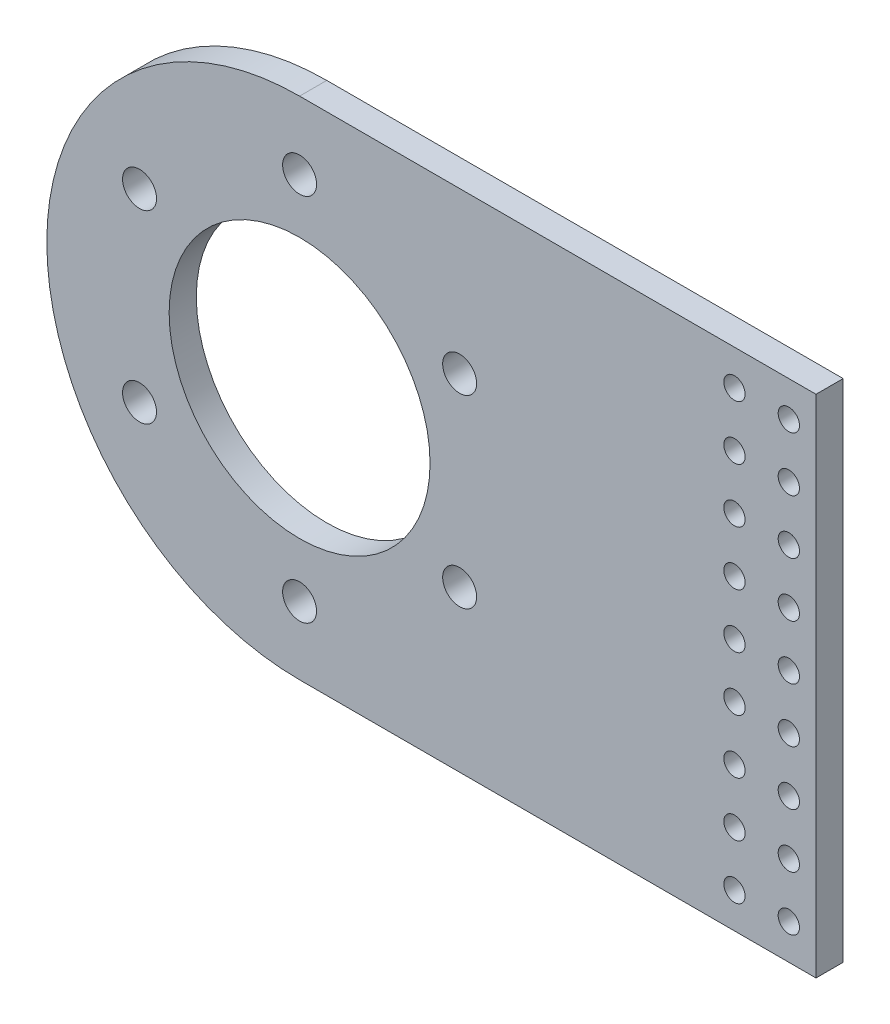
SolidWorks part; units mm, degrees
ref_plane "Front Plane" through (0, 0, 0) normal (1, 0, 0) x (0, 1, 0)
ref_plane "Top Plane" through (0, 0, 0) normal (0, 0, 1) x (0, 1, 0)
ref_plane "Right Plane" through (0, 0, 0) normal (0, 1, 0) x (-1, 0, 0)
sketch "Sketch1" plane through (0, 0, 0) normal (0, 0, 1) x (0, 1, 0)
  line L0 (-59.055, 0) -> (-59.055, -120.65)
  line L1 (-59.055, -120.65) -> (59.055, -120.65)
  line L2 (59.055, -120.65) -> (59.055, 0)
  circle A0 centre (0, 0) radius 25.4 construction
  circle A1 centre (0, 0) radius 27.305 construction
  circle A2 centre (0, 0) radius 43.18 construction
  circle A3 centre (-43.18, 0) radius 15.875 construction
  circle A4 centre (-21.59, 37.395) radius 15.875 construction
  circle A5 centre (21.59, 37.395) radius 15.875 construction
  circle A6 centre (43.18, 0) radius 15.875 construction
  circle A7 centre (21.59, -37.395) radius 15.875 construction
  circle A8 centre (-21.59, -37.395) radius 15.875 construction
  arc A9 (59.055, 0) -> (-59.055, 0) centre (0, 0) ccw
  circle A10 centre (0, 0) radius 30.48
  point P5 (-43.18, 0)
  point P8 (-21.59, 37.395)
  point P13 (21.59, 37.395)
  point P16 (43.18, 0)
  point P19 (21.59, -37.395)
  point P22 (-21.59, -37.395)
  point P25 (0, 0)
  dimension "D1" = 50.8
  dimension "D2" = 1.905
  dimension "D3" = 15.875
  dimension "D4" = 31.75
  dimension "D5" = 6
  dimension "D6" = 3.175
  dimension "D7" = 120.65
extrude "Boss-Extrude1" add sketch "Sketch1" along normal blind 6.35
sketch "Sketch2" plane through (0, 0, 6.35) normal (0, 0, 1) x (1, 0, 0)
  line L0 (120.65, -59.055) -> (120.65, 59.055) construction
  point P0 (114.3, -50.8)
  point P8 (101.6, -50.8)
  point P9 (101.6, -38.1)
  point P10 (101.6, -25.4)
  point P11 (101.6, -12.7)
  point P12 (101.6, 0)
  point P13 (101.6, 12.7)
  point P14 (101.6, 25.4)
  point P15 (101.6, 38.1)
  point P16 (101.6, 50.8)
  point P17 (114.3, -38.1)
  point P18 (114.3, -25.4)
  point P19 (114.3, -12.7)
  point P20 (114.3, 0)
  point P21 (114.3, 12.7)
  point P22 (114.3, 25.4)
  point P23 (114.3, 38.1)
  point P24 (114.3, 50.8)
  dimension "D1" = 6.35
  dimension "D2" = 2
  dimension "D5" = 12.7
  dimension "D6" = 12.7
  dimension "D4" = 9
hole_wizard "#9 (0.196) Diameter Hole1" positions "Sketch2" profile "Sketch3" hole size "#9" standard "ANSI Inch" end condition through all
sketch "Sketch3" plane through (114.3, -50.8, 6.35) normal (1, 0, 0) x (0, -1, 0)
  line L0 (0, 0) -> (0, 6.35)
  line L1 (0, 6.35) -> (2.4892, 6.35)
  line L2 (2.4892, 6.35) -> (2.4892, 0)
  line L5 (2.4892, 0) -> (0, 0)
  line L11 (0, -6.35) -> (0, 107.95) construction
  dimension "Thru Hole Dia." = 4.9784
  dimension "Thru Hole Depth" = 6.35
sketch "Sketch4" plane through (0, 0, 6.35) normal (0, 0, 1) x (1, 0, 0)
  point P0 (37.395, 21.59)
  point P2 (37.395, -21.59)
  point P4 (0, -43.18)
  point P6 (-37.395, -21.59)
  point P8 (-37.395, 21.59)
  point P10 (0, 43.18)
hole_wizard "5/16 (0.3125) Diameter Hole1" positions "Sketch4" profile "Sketch5" hole size "5/16" standard "ANSI Inch" end condition through all
sketch "Sketch5" plane through (37.395, 21.59, 6.35) normal (1, 0, 0) x (0, -1, 0)
  line L0 (0, 0) -> (0, 6.35)
  line L1 (0, 6.35) -> (3.9688, 6.35)
  line L2 (3.9688, 6.35) -> (3.9688, 0)
  line L5 (3.9688, 0) -> (0, 0)
  line L11 (0, -6.35) -> (0, 107.95) construction
  dimension "Thru Hole Dia." = 7.9375
  dimension "Thru Hole Depth" = 6.35
